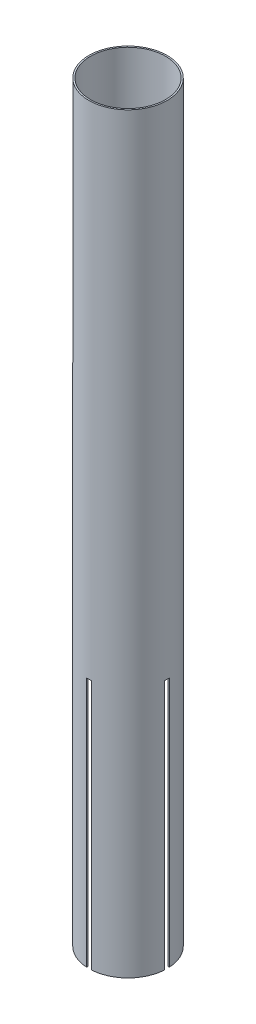
SolidWorks part; units mm, degrees
material "S-Glass Fiber"
ref_plane "Front Plane" through (0, 0, 0) normal (0, 0, 1) x (1, 0, 0)
ref_plane "Top Plane" through (0, 0, 0) normal (0, 1, 0) x (1, 0, 0)
ref_plane "Right Plane" through (0, 0, 0) normal (1, 0, 0) x (0, 0, -1)
sketch "Sketch1" plane through (0, 0, 0) normal (0, 1, 0) x (1, 0, 0)
  circle A0 centre (0, 0) radius 39.624
  circle A1 centre (0, 0) radius 38.1
  dimension "D1" = 79.248
  dimension "D2" = 76.2
extrude "Boss-Extrude1" add sketch "Sketch1" along normal blind 762
sketch "Sketch2" plane through (0, 0, 0) normal (0, 0, 1) x (1, 0, 0)
  line L0 (-2.3813, 0) -> (2.3812, 0)
  line L1 (-39.624, 0) -> (39.624, 0) construction
  line L2 (2.3812, 0) -> (2.3812, 254)
  line L3 (2.3812, 254) -> (-2.3813, 254)
  line L4 (-2.3813, 254) -> (-2.3813, -1.7067)
  point P6 (0, 0)
  point P8 (0, 0)
  dimension "D1" = 4.7625
  dimension "D2" = 254
extrude "Cut-Extrude1" cut sketch "Sketch2" against normal through all both and the other way through all contours L3 L4 L0 L2 region at (0, 127, 0)
pattern_circular "CirPattern1" count 2 over 90 about axis through (0, 762, 0) along (0, -1, 0) of "Cut-Extrude1" reverse direction yes
